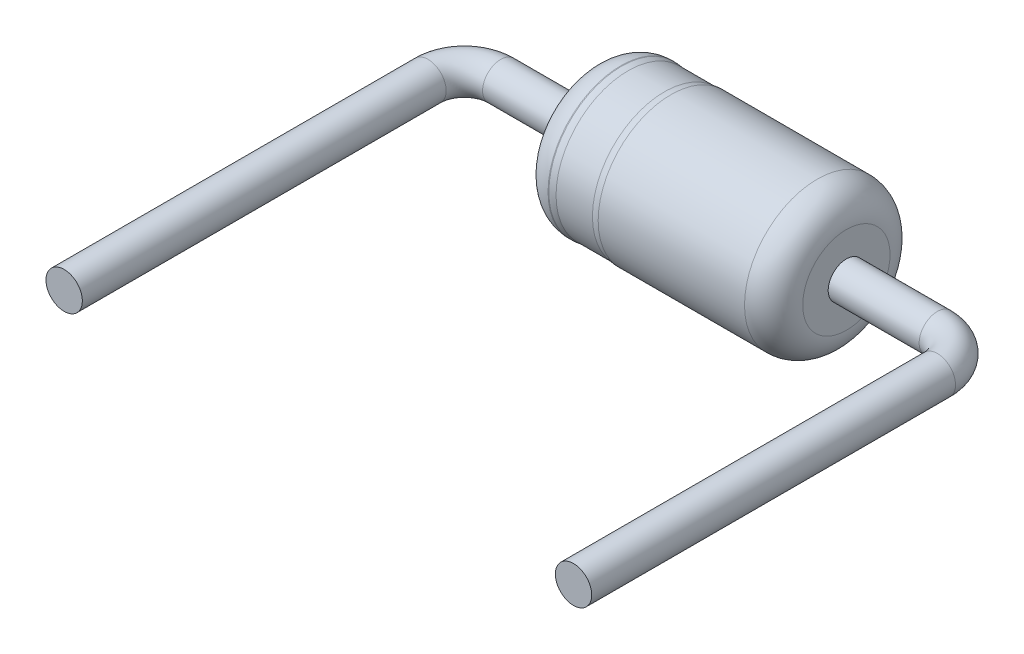
SolidWorks part; units mm, degrees
ref_plane "Ön Düzlem" through (0, 0, 0) normal (0, 0, 1) x (1, 0, 0)
ref_plane "Üst Düzlem" through (0, 0, 0) normal (0, 1, 0) x (1, 0, 0)
ref_plane "Sağ Düzlem" through (0, 0, 0) normal (1, 0, 0) x (0, 0, -1)
sketch "Çizim3" plane through (0, 0, 0) normal (0, 1, 0) x (1, 0, 0)
  line L0 (-0.75, -1) -> (1.75, -1)
  line L1 (-1.75, 0) -> (1.75, 0)
  line L2 (-1.75, 0) -> (-1.75, -1)
  line L3 (-1.75, -1) -> (-1.25, -1)
  line L4 (1.75, 0) -> (1.75, -1)
  line L6 (-1.25, -1) -> (-1.25, -0.99)
  line L7 (-1.25, -0.99) -> (-0.75, -0.99)
  line L8 (-0.75, -1) -> (-0.75, -0.99)
  dimension "D1" = 3.5
  dimension "D2" = 1
  dimension "D3" = 1
  dimension "D4" = 1.75
  dimension "D5" = 0.5
  dimension "D6" = 0.01
  dimension "D7" = 0.5
revolve "Döndür2" add sketch "Çizim3" angle 360 about L1
sketch "Çizim4" plane through (0, 0, 0) normal (0, 1, 0) x (1, 0, 0)
  line L0 (-1.5787, 0) -> (-3, 0)
  line L1 (-3.5, -0.5) -> (-3.5, -5.5)
  line L2 (-1.75, 1) -> (-1.75, -1) construction
  arc A0 (-3, 0) -> (-3.5, -0.5) centre (-3, -0.5) ccw
  dimension "D1" = 1.25
  dimension "D2" = 5
ref_plane "Düzlem1" through (-1.5787, 0, 0) normal (-1, 0, 0) x (0, 0, 1)
sketch "Çizim5" plane through (-1.5787, 0, 0) normal (-1, 0, 0) x (0, 0, 1)
  circle A0 centre (0, 0) radius 0.25
sweep "Süpür1" add profiles "Çizim5" path "Çizim4"
sketch "Çizim6" plane through (0, 0, 0) normal (0, 1, 0) x (1, 0, 0)
  line L0 (1.5194, 0) -> (3, 0)
  line L1 (3.5, -0.5) -> (3.5, -5.5)
  line L2 (1.75, -1) -> (1.75, 1) construction
  arc A0 (3.5, -0.5) -> (3, 0) centre (3, -0.5) ccw
  dimension "D1" = 1.25
  dimension "D2" = 5
ref_plane "Düzlem2" through (1.5194, 0, 0) normal (1, 0, 0) x (0, 0, -1)
sketch "Çizim7" plane through (1.5194, 0, 0) normal (1, 0, 0) x (0, 0, -1)
  circle A0 centre (0, 0) radius 0.25
sweep "Süpür2" add profiles "Çizim7" path "Çizim6"
fillet "Radyus1" radius 0.4 2 edges at (-0.75, 0, 1) (1.75, 0, 1)
fillet "Radyus2" radius 0.4 2 edges at (-1.75, 0, 1) (-1.25, 0, 1)
